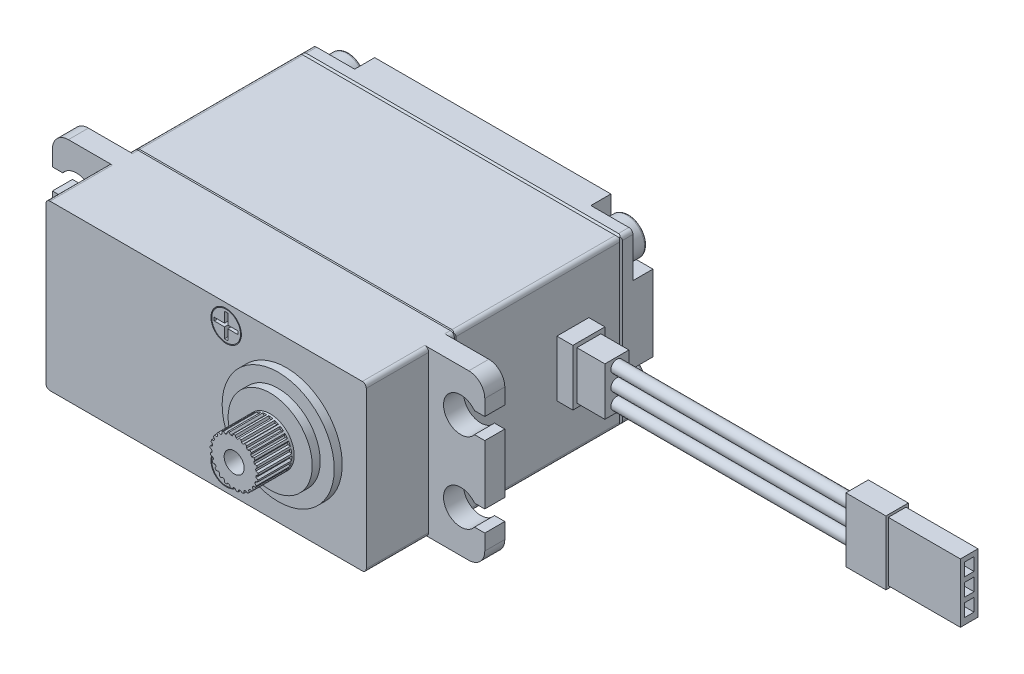
SolidWorks part; units mm, degrees
ref_plane "前视基准面" through (0, 0, 0) normal (0, 0, 1) x (1, 0, 0)
ref_plane "上视基准面" through (0, 0, 0) normal (0, 1, 0) x (1, 0, 0)
ref_plane "右视基准面" through (0, 0, 0) normal (1, 0, 0) x (0, 0, -1)
sketch "草图1" plane through (0, 0, 0) normal (0, 0, 1) x (1, 0, 0)
  line L1 (-20, 10.25) -> (20, 10.25)
  line L2 (-20, 10.25) -> (-20, -10.25)
  line L3 (-20, -10.25) -> (20, -10.25)
  line L4 (20, 10.25) -> (20, -10.25)
  dimension "D1" = 10.25
  dimension "D2" = 20.5
  dimension "D3" = 20
  dimension "D4" = 40
extrude "凸台-拉伸1" add sketch "草图1" along normal blind 4
chamfer "倒角1" distance 0.2 angle 45 4 edges at (0, 10.25, 4) (20, 0, 4) (0, -10.25, 4) (-20, 0, 4)
sketch "草图2" plane through (0, 0, 4) normal (0, 0, 1) x (1, 0, 0)
  line L0 (20, 10.25) -> (20, -10.25) construction
  line L1 (20, -10.25) -> (-20, -10.25) construction
  line L2 (-20, -10.25) -> (-20, 10.25) construction
  line L3 (-20, 10.25) -> (20, 10.25) construction
  line L4 (20, 10.25) -> (20, -10.25)
  line L5 (20, -10.25) -> (-20, -10.25)
  line L6 (-20, -10.25) -> (-20, 10.25)
  line L7 (-20, 10.25) -> (20, 10.25)
extrude "凸台-拉伸2" add sketch "草图2" along normal blind 20.8
chamfer "倒角4" distance 0.2 angle 45 4 edges at (-20, 0, 4) (0, 10.25, 4) (20, 0, 4) (0, -10.25, 4)
chamfer "倒角5" distance 0.2 angle 45 4 edges at (20, 0, 24.8) (0, -10.25, 24.8) (-20, 0, 24.8) (0, 10.25, 24.8)
sketch "草图3" plane through (0, 0, 24.8) normal (0, 0, 1) x (1, 0, 0)
  line L0 (20, 10.25) -> (20, -10.25) construction
  line L1 (20, -10.25) -> (-20, -10.25) construction
  line L2 (-20, -10.25) -> (-20, 10.25) construction
  line L3 (-20, 10.25) -> (20, 10.25) construction
  line L4 (20, 10.25) -> (20, -10.25)
  line L5 (20, -10.25) -> (-20, -10.25)
  line L6 (-20, -10.25) -> (-20, 10.25)
  line L7 (-20, 10.25) -> (20, 10.25)
extrude "凸台-拉伸3" add sketch "草图3" along normal blind 11
sketch "草图4" plane through (0, 0, 35.8) normal (0, 0, 1) x (1, 0, 0)
  line L0 (20, -10.25) -> (20, 10.25) construction
  circle A0 centre (10, 0) radius 7
  dimension "D1" = 10
  dimension "D2" = 14
extrude "凸台-拉伸4" add sketch "草图4" along normal blind 2
sketch "草图5" plane through (0, 0, 37.8) normal (0, 0, 1) x (1, 0, 0)
  circle A0 centre (10, 0) radius 3
  dimension "D1" = 6
extrude "凸台-拉伸5" add sketch "草图5" along normal blind 4.5
ref_plane "基准面1" through (0, 0, 23) normal (0, 0, 1) x (1, 0, 0)
sketch "草图11" plane through (0, 0, 42.3) normal (0, 0, 1) x (1, 0, 0)
  circle A0 centre (10, 0) radius 1.25
  dimension "D1" = 2.5
extrude "切除-拉伸7" cut sketch "草图11" against normal blind 6
sketch "草图12" plane through (0, 0, 42.3) normal (0, 0, 1) x (1, 0, 0)
  line L1 (9.76, 2.7395) -> (9.88, 2.9976)
  line L2 (10.24, 2.7395) -> (10.12, 2.9976)
  line L3 (10.9137, 2.5938) -> (10.8617, 2.8736)
  line L4 (10.4488, 2.7131) -> (10.6292, 2.9333)
  line L5 (11.5301, 2.285) -> (11.5493, 2.569)
  line L6 (11.1095, 2.5163) -> (11.3389, 2.6846)
  line L7 (12.0503, 1.8327) -> (12.1395, 2.103)
  line L8 (11.7004, 2.1613) -> (11.9645, 2.2673)
  line L9 (12.4416, 1.2653) -> (12.5953, 1.5049)
  line L10 (12.1844, 1.6705) -> (12.4667, 1.7075)
  line L11 (12.6796, 0.6183) -> (12.888, 0.8122)
  line L12 (12.5313, 1.0748) -> (12.8138, 1.0404)
  line L13 (12.7492, -0.0675) -> (12.9992, 0.0685)
  line L14 (12.719, 0.4115) -> (12.9841, 0.308)
  line L15 (12.646, -0.7491) -> (12.922, -0.6796)
  line L16 (12.736, -0.2776) -> (12.967, -0.4438)
  line L17 (12.3766, -1.3836) -> (12.6612, -1.3849)
  line L18 (12.581, -0.9493) -> (12.7634, -1.1677)
  line L19 (11.9578, -1.9312) -> (12.2332, -2.0032)
  line L20 (12.2638, -1.5613) -> (12.3862, -1.8183)
  line L21 (11.4161, -2.3574) -> (11.6649, -2.4956)
  line L22 (11.8044, -2.0752) -> (11.859, -2.3546)
  line L23 (10.7853, -2.6355) -> (10.9919, -2.8313)
  line L24 (11.2316, -2.4588) -> (11.2151, -2.7429)
  line L25 (10.1052, -2.748) -> (10.2566, -2.989)
  line L26 (10.5815, -2.6878) -> (10.4948, -2.9589)
  line L27 (9.4185, -2.6878) -> (9.5052, -2.9589)
  line L28 (9.8948, -2.748) -> (9.7434, -2.989)
  line L29 (8.7684, -2.4588) -> (8.7849, -2.7429)
  line L30 (9.2147, -2.6355) -> (9.0081, -2.8313)
  line L31 (8.1956, -2.0752) -> (8.141, -2.3546)
  line L32 (8.5839, -2.3574) -> (8.3351, -2.4956)
  line L33 (7.7362, -1.5613) -> (7.6138, -1.8183)
  line L34 (8.0422, -1.9312) -> (7.7668, -2.0032)
  line L35 (7.419, -0.9493) -> (7.2366, -1.1677)
  line L36 (7.6234, -1.3836) -> (7.3388, -1.3849)
  line L37 (7.264, -0.2776) -> (7.033, -0.4438)
  line L38 (7.354, -0.7491) -> (7.078, -0.6796)
  line L39 (7.281, 0.4115) -> (7.0159, 0.308)
  line L40 (7.2508, -0.0675) -> (7.0008, 0.0685)
  line L41 (7.4687, 1.0748) -> (7.1862, 1.0404)
  line L42 (7.3204, 0.6183) -> (7.112, 0.8122)
  line L43 (7.8156, 1.6705) -> (7.5333, 1.7075)
  line L44 (7.5584, 1.2653) -> (7.4047, 1.5049)
  line L45 (8.2996, 2.1613) -> (8.0355, 2.2673)
  line L46 (7.9497, 1.8327) -> (7.8605, 2.103)
  line L47 (8.8905, 2.5163) -> (8.6611, 2.6846)
  line L48 (8.4699, 2.285) -> (8.4507, 2.569)
  line L49 (9.5512, 2.7131) -> (9.3708, 2.9333)
  line L50 (9.0863, 2.5938) -> (9.1383, 2.8736)
  arc A0 (9.76, 2.7395) -> (9.5512, 2.7131) centre (10, 0) ccw
  arc A1 (9.0863, 2.5938) -> (8.8905, 2.5163) centre (10, 0) ccw
  circle A2 centre (10, 0) radius 3 construction
  arc A3 (9.88, 2.9976) -> (9.3708, 2.9333) centre (10, 0) ccw
  arc A4 (9.1383, 2.8736) -> (8.6611, 2.6846) centre (10, 0) ccw
  arc A5 (8.4699, 2.285) -> (8.2996, 2.1613) centre (10, 0) ccw
  arc A6 (8.4507, 2.569) -> (8.0355, 2.2673) centre (10, 0) ccw
  arc A7 (7.9497, 1.8327) -> (7.8156, 1.6705) centre (10, 0) ccw
  arc A8 (7.8605, 2.103) -> (7.5333, 1.7075) centre (10, 0) ccw
  arc A9 (7.5584, 1.2653) -> (7.4687, 1.0748) centre (10, 0) ccw
  arc A10 (7.4047, 1.5049) -> (7.1862, 1.0404) centre (10, 0) ccw
  arc A11 (7.3204, 0.6183) -> (7.281, 0.4115) centre (10, 0) ccw
  arc A12 (7.112, 0.8122) -> (7.0159, 0.308) centre (10, 0) ccw
  arc A13 (7.2508, -0.0675) -> (7.264, -0.2776) centre (10, 0) ccw
  arc A14 (7.0008, 0.0685) -> (7.033, -0.4438) centre (10, 0) ccw
  arc A15 (7.354, -0.7491) -> (7.419, -0.9493) centre (10, 0) ccw
  arc A16 (7.078, -0.6796) -> (7.2366, -1.1677) centre (10, 0) ccw
  arc A17 (7.3388, -1.3849) -> (7.6138, -1.8183) centre (10, 0) ccw
  arc A18 (7.6234, -1.3836) -> (7.7362, -1.5613) centre (10, 0) ccw
  arc A19 (8.0422, -1.9312) -> (8.1956, -2.0752) centre (10, 0) ccw
  arc A20 (7.7668, -2.0032) -> (8.141, -2.3546) centre (10, 0) ccw
  arc A21 (8.5839, -2.3574) -> (8.7684, -2.4588) centre (10, 0) ccw
  arc A22 (8.3351, -2.4956) -> (8.7849, -2.7429) centre (10, 0) ccw
  arc A23 (9.2147, -2.6355) -> (9.4185, -2.6878) centre (10, 0) ccw
  arc A24 (9.0081, -2.8313) -> (9.5052, -2.9589) centre (10, 0) ccw
  arc A25 (9.8948, -2.748) -> (10.1052, -2.748) centre (10, 0) ccw
  arc A26 (9.7434, -2.989) -> (10.2566, -2.989) centre (10, 0) ccw
  arc A27 (10.5815, -2.6878) -> (10.7853, -2.6355) centre (10, 0) ccw
  arc A28 (10.4948, -2.9589) -> (10.9919, -2.8313) centre (10, 0) ccw
  arc A29 (11.2316, -2.4588) -> (11.4161, -2.3574) centre (10, 0) ccw
  arc A30 (11.2151, -2.7429) -> (11.6649, -2.4956) centre (10, 0) ccw
  arc A31 (11.8044, -2.0752) -> (11.9578, -1.9312) centre (10, 0) ccw
  arc A32 (11.859, -2.3546) -> (12.2332, -2.0032) centre (10, 0) ccw
  arc A33 (12.3862, -1.8183) -> (12.6612, -1.3849) centre (10, 0) ccw
  arc A34 (12.2638, -1.5613) -> (12.3766, -1.3836) centre (10, 0) ccw
  arc A35 (12.7634, -1.1677) -> (12.922, -0.6796) centre (10, 0) ccw
  arc A36 (12.581, -0.9493) -> (12.646, -0.7491) centre (10, 0) ccw
  arc A37 (12.967, -0.4438) -> (12.9992, 0.0685) centre (10, 0) ccw
  arc A38 (12.736, -0.2776) -> (12.7492, -0.0675) centre (10, 0) ccw
  arc A39 (12.9841, 0.308) -> (12.888, 0.8122) centre (10, 0) ccw
  arc A40 (12.719, 0.4115) -> (12.6796, 0.6183) centre (10, 0) ccw
  arc A41 (12.5313, 1.0748) -> (12.4416, 1.2653) centre (10, 0) ccw
  arc A42 (12.8138, 1.0404) -> (12.5953, 1.5049) centre (10, 0) ccw
  arc A43 (12.1844, 1.6705) -> (12.0503, 1.8327) centre (10, 0) ccw
  arc A44 (12.4667, 1.7075) -> (12.1395, 2.103) centre (10, 0) ccw
  arc A45 (11.7004, 2.1613) -> (11.5301, 2.285) centre (10, 0) ccw
  arc A46 (11.9645, 2.2673) -> (11.5493, 2.569) centre (10, 0) ccw
  arc A47 (11.1095, 2.5163) -> (10.9137, 2.5938) centre (10, 0) ccw
  arc A48 (11.3389, 2.6846) -> (10.8617, 2.8736) centre (10, 0) ccw
  arc A49 (10.4488, 2.7131) -> (10.24, 2.7395) centre (10, 0) ccw
  arc A50 (10.6292, 2.9333) -> (10.12, 2.9976) centre (10, 0) ccw
  point P111 (10, 0)
  dimension "D1" = 5.5
  dimension "D4" = 25
extrude "切除-拉伸8" cut sketch "草图12" against normal blind 4.2
sketch "草图17" plane through (20, 0, 0) normal (1, 0, 0) x (0, 0, -1)
  line L2 (-12, 3.5) -> (-8, 3.5)
  line L3 (-12, 3.5) -> (-12, -3.5)
  line L4 (-12, -3.5) -> (-8, -3.5)
  line L5 (-8, 3.5) -> (-8, -3.5)
  dimension "D2" = 7
  dimension "D3" = 3.5
  dimension "D4" = 4
extrude "凸台-拉伸8" add sketch "草图17" along normal blind 2
sketch "草图18" plane through (22, 0, 0) normal (1, 0, 0) x (0, 0, -1)
  line L8 (-11.5, 3) -> (-11.5, -3)
  line L9 (-11.5, -3) -> (-8.5, -3)
  line L10 (-8.5, -3) -> (-8.5, 3)
  line L11 (-8.5, 3) -> (-11.5, 3)
  line L12 (-11.5, 3) -> (-11.5, -3)
  line L13 (-11.5, -3) -> (-8.5, -3)
  line L14 (-8.5, -3) -> (-8.5, 3)
  line L15 (-8.5, 3) -> (-11.5, 3)
  dimension "D1" = 0.5
extrude "凸台-拉伸9" add sketch "草图18" along normal blind 3.5
sketch "草图19" plane through (25.5, 0, 0) normal (1, 0, 0) x (0, 0, -1)
  line L0 (-8.5, -3) -> (-8.5, 3) construction
  line L1 (-8.5, -3) -> (-8.5, 3) construction
  line L2 (-8.5, 3) -> (-11.5, 3) construction
  circle A0 centre (-10, 0) radius 0.75
  circle A1 centre (-10, 2) radius 0.75
  circle A2 centre (-10, -2) radius 0.75
  dimension "D1" = 1.5
  dimension "D2" = 1.5
  dimension "D3" = 1.5
  dimension "D4" = 1.5
  dimension "D5" = 1.5
  dimension "D6" = 1.5
  dimension "D7" = 1
  dimension "D8" = 2
  dimension "D9" = 2
extrude "凸台-拉伸10" add sketch "草图19" along normal blind 30
sketch "草图20" plane through (55.5, 0, 0) normal (1, 0, 0) x (0, 0, -1)
  line L1 (-11.4, 4) -> (-8.6, 4)
  line L2 (-11.4, 4) -> (-11.4, -4)
  line L3 (-11.4, -4) -> (-8.6, -4)
  line L4 (-8.6, 4) -> (-8.6, -4)
  circle A0 centre (-10, 2) radius 0.75 construction
  dimension "D1" = 8
  dimension "D2" = 2.8
  dimension "D3" = 1.4
  dimension "D4" = 4
extrude "凸台-拉伸11" add sketch "草图20" along normal blind 5
sketch "草图21" plane through (60.5, 0, 0) normal (1, 0, 0) x (0, 0, -1)
  line L5 (-10.59, 3.1) -> (-9.4, 3.1)
  line L6 (-10.59, 3.1) -> (-10.59, 1.5)
  line L7 (-10.59, 1.5) -> (-9.4, 1.5)
  line L8 (-11.1, 3.7) -> (-11.1, -3.7)
  line L9 (-11.1, -3.7) -> (-8.9, -3.7)
  line L10 (-8.9, -3.7) -> (-8.9, 3.7)
  line L11 (-8.9, 3.7) -> (-11.1, 3.7)
  line L12 (-11.1, 3.7) -> (-11.1, -3.7)
  line L13 (-11.1, -3.7) -> (-8.9, -3.7)
  line L14 (-8.9, -3.7) -> (-8.9, 3.7)
  line L15 (-8.9, 3.7) -> (-11.1, 3.7)
  line L16 (-9.4, 3.1) -> (-9.4, 1.5)
  line L17 (-10.59, 0.9) -> (-9.4, 0.9)
  line L18 (-10.59, 0.9) -> (-10.59, -0.7)
  line L19 (-10.59, -0.7) -> (-9.4, -0.7)
  line L20 (-9.4, 0.9) -> (-9.4, -0.7)
  line L21 (-10.59, -1.3) -> (-9.4, -1.3)
  line L22 (-10.59, -1.3) -> (-10.59, -2.9)
  line L23 (-10.59, -2.9) -> (-9.4, -2.9)
  line L24 (-9.4, -1.3) -> (-9.4, -2.9)
  dimension "D2" = 1.6
  dimension "D3" = 1.6
  dimension "D4" = 1.6
  dimension "D5" = 0.5
  dimension "D6" = 0.5
  dimension "D7" = 0.5
  dimension "D8" = 0.6
  dimension "D9" = 0.6
  dimension "D10" = 0.6
  dimension "D1" = 0.3
extrude "凸台-拉伸12" add sketch "草图21" along normal blind 9
sketch "草图22" plane through (0, 0, 0) normal (0, 0, -1) x (-1, 0, 0)
  line L5 (-20, 4.75) -> (-20, 10.25)
  line L6 (-20, 10.25) -> (-14.75, 10.25)
  line L7 (-17.5, -4.75) -> (-20, -4.75)
  line L8 (-14.75, -7.5) -> (-14.75, -10.25)
  line L9 (-20, -4.75) -> (-20, -10.25)
  line L11 (-20, -10.25) -> (-14.75, -10.25)
  line L12 (-14.75, 7.5) -> (-14.75, 10.25)
  line L13 (-17.5, 4.75) -> (-20, 4.75)
  line L14 (14.75, -7.5) -> (14.75, -10.25)
  line L15 (20, -10.25) -> (14.75, -10.25)
  line L16 (20, -4.75) -> (20, -10.25)
  line L17 (17.5, -4.75) -> (20, -4.75)
  line L18 (20, 4.75) -> (20, 10.25)
  line L19 (17.5, 4.75) -> (20, 4.75)
  line L20 (14.75, 7.5) -> (14.75, 10.25)
  line L21 (20, 10.25) -> (14.75, 10.25)
  arc A0 (-14.75, -7.5) -> (-17.5, -4.75) centre (-17.5, -7.5) ccw
  arc A1 (-14.75, 7.5) -> (-17.5, 4.75) centre (-17.5, 7.5) cw
  arc A2 (14.75, -7.5) -> (17.5, -4.75) centre (17.5, -7.5) cw
  arc A3 (14.75, 7.5) -> (17.5, 4.75) centre (17.5, 7.5) ccw
  dimension "D3" = 5.5
extrude "切除-拉伸13" cut sketch "草图22" against normal blind 2.5
sketch "草图23" plane through (0, 0, 2.5) normal (0, 0, -1) x (-1, 0, 0)
  line L4 (-17.25, -7.75) -> (-15.6165, -7.75)
  line L5 (-17.25, -7.25) -> (-15.6165, -7.25)
  line L6 (-17.25, 7.25) -> (-17.25, 5.6165)
  line L7 (-17.25, 7.75) -> (-15.6165, 7.75)
  line L8 (-17.25, -7.25) -> (-17.25, -5.6165)
  line L9 (-17.75, 7.25) -> (-17.75, 5.6165)
  line L10 (-17.75, -7.25) -> (-17.75, -5.6165)
  line L11 (-17.25, 7.25) -> (-15.6165, 7.25)
  line L12 (-19.3835, -7.25) -> (-17.75, -7.25)
  line L13 (-19.3835, -7.75) -> (-17.75, -7.75)
  line L14 (-17.75, -9.3835) -> (-17.75, -7.75)
  line L15 (-17.25, -9.3835) -> (-17.25, -7.75)
  line L16 (-19.3835, 7.25) -> (-17.75, 7.25)
  line L17 (-19.3835, 7.75) -> (-17.75, 7.75)
  line L18 (-17.25, 9.3835) -> (-17.25, 7.75)
  line L19 (-17.75, 9.3835) -> (-17.75, 7.75)
  line L20 (17.25, -7.25) -> (15.6165, -7.25)
  line L21 (17.25, -7.75) -> (15.6165, -7.75)
  line L22 (17.25, -9.3835) -> (17.25, -7.75)
  line L23 (17.75, -9.3835) -> (17.75, -7.75)
  line L24 (19.3835, -7.75) -> (17.75, -7.75)
  line L25 (19.3835, -7.25) -> (17.75, -7.25)
  line L26 (17.75, -7.25) -> (17.75, -5.6165)
  line L27 (17.25, -7.25) -> (17.25, -5.6165)
  line L28 (19.3835, 7.25) -> (17.75, 7.25)
  line L29 (17.75, 7.25) -> (17.75, 5.6165)
  line L30 (17.25, 7.25) -> (17.25, 5.6165)
  line L31 (17.25, 7.25) -> (15.6165, 7.25)
  line L32 (17.25, 7.75) -> (15.6165, 7.75)
  line L33 (17.25, 9.3835) -> (17.25, 7.75)
  line L34 (17.75, 9.3835) -> (17.75, 7.75)
  line L35 (19.3835, 7.75) -> (17.75, 7.75)
  circle A0 centre (-17.5, 7.5) radius 2.25
  arc A1 (-15.6165, 7.25) -> (-15.6165, 7.75) centre (-17.5, 7.5) ccw
  arc A2 (-17.75, 5.6165) -> (-17.25, 5.6165) centre (-17.5, 7.5) ccw
  arc A3 (-19.3835, 7.75) -> (-19.3835, 7.25) centre (-17.5, 7.5) ccw
  arc A4 (-17.25, 9.3835) -> (-17.75, 9.3835) centre (-17.5, 7.5) ccw
  arc A5 (-17.75, -5.6165) -> (-17.25, -5.6165) centre (-17.5, -7.5) cw
  arc A6 (-15.6165, -7.25) -> (-15.6165, -7.75) centre (-17.5, -7.5) cw
  arc A7 (-19.3835, -7.75) -> (-19.3835, -7.25) centre (-17.5, -7.5) cw
  arc A8 (-17.25, -9.3835) -> (-17.75, -9.3835) centre (-17.5, -7.5) cw
  circle A9 centre (-17.5, -7.5) radius 2.25
  arc A10 (15.6165, -7.25) -> (15.6165, -7.75) centre (17.5, -7.5) ccw
  arc A11 (17.25, -9.3835) -> (17.75, -9.3835) centre (17.5, -7.5) ccw
  arc A12 (19.3835, -7.75) -> (19.3835, -7.25) centre (17.5, -7.5) ccw
  arc A13 (17.75, -5.6165) -> (17.25, -5.6165) centre (17.5, -7.5) ccw
  circle A14 centre (17.5, -7.5) radius 2.25
  arc A15 (17.75, 5.6165) -> (17.25, 5.6165) centre (17.5, 7.5) cw
  arc A16 (19.3835, 7.75) -> (19.3835, 7.25) centre (17.5, 7.5) cw
  arc A17 (15.6165, 7.25) -> (15.6165, 7.75) centre (17.5, 7.5) cw
  arc A18 (17.25, 9.3835) -> (17.75, 9.3835) centre (17.5, 7.5) cw
  circle A19 centre (17.5, 7.5) radius 2.25
  point P8 (-19.75, 7.25)
  point P9 (-13.9428, 7.25)
  point P10 (-17.75, 9.75)
  point P11 (-17.75, 5.25)
  point P12 (-19.75, 7.75)
  point P13 (-13.9428, 7.75)
  point P14 (-17.25, 9.75)
  point P15 (-17.25, 5.25)
  dimension "D1" = 4.5
  dimension "D2" = 3.8
extrude "凸台-拉伸13" add sketch "草图23" along normal blind 2
fillet "圆角2" radius 0.3 4 edges at (-19.75, -7.5, 0.5) (19.75, -7.5, 0.5) (15.25, 7.5, 0.5) (-15.25, 7.5, 0.5)
chamfer "倒角6" distance 0.5 angle 45 1 edges at (17, 0, 37.8)
fillet "圆角6" radius 0.5 4 edges at (20, 10.25, 30.3) (20, -10.25, 30.3) (-20, 10.25, 30.3) (-20, -10.25, 30.3)
fillet "圆角7" radius 0.5 4 edges at (20, -10.25, 14.4) (20, 10.25, 14.4) (-20, 10.25, 14.4) (-20, -10.25, 14.4)
fillet "圆角8" radius 0.5 4 edges at (20, 10.25, 3.15) (-20, 10.25, 3.15) (-20, -10.25, 3.15) (20, -10.25, 3.15)
sketch "草图24" plane through (0, 0, 37.8) normal (0, 0, 1) x (1, 0, 0)
  circle A0 centre (10, 0) radius 5.25
  circle A3 centre (10, 0) radius 7 construction
  circle A4 centre (10, 0) radius 7
  dimension "D1" = 10.5
extrude "切除-拉伸14" cut sketch "草图24" against normal blind 1
ref_plane "基准面2" through (0, 0, 25.5) normal (0, 0, -1) x (-1, 0, 0)
sketch "草图25" plane through (0, 0, 25.5) normal (0, 0, -1) x (-1, 0, 0)
  line L5 (27, 10.25) -> (27, 6.3)
  line L6 (19.5, 10.25) -> (27, 10.25)
  line L8 (19.5, -10.25) -> (27, -10.25)
  line L10 (20, 4.75) -> (20, 9.75) construction
  line L11 (20, 4.75) -> (20, 9.75)
  line L12 (20, 9.75) -> (20, -9.75)
  line L13 (25.7125, -3.7) -> (27, -3.7)
  line L15 (25.7125, 3.7) -> (27, 3.7)
  line L16 (25.7125, 6.3) -> (27, 6.3)
  line L17 (27, 3.7) -> (27, -3.7)
  line L18 (25.7125, -6.3) -> (27, -6.3)
  line L19 (27, -6.3) -> (27, -10.25)
  line L20 (-27, -6.3) -> (-27, -10.25)
  line L21 (-25.7125, -6.3) -> (-27, -6.3)
  line L22 (-27, 3.7) -> (-27, -3.7)
  line L23 (-25.7125, 6.3) -> (-27, 6.3)
  line L24 (-25.7125, 3.7) -> (-27, 3.7)
  line L25 (-25.7125, -3.7) -> (-27, -3.7)
  line L26 (-20, 9.75) -> (-20, -9.75)
  line L27 (-20, 4.75) -> (-20, 9.75)
  line L28 (-19.5, -10.25) -> (-27, -10.25)
  line L29 (-19.5, 10.25) -> (-27, 10.25)
  line L30 (-27, 10.25) -> (-27, 6.3)
  arc A0 (20, 9.75) -> (19.5, 10.25) centre (19.5, 9.75) ccw construction
  arc A1 (20, 9.75) -> (19.5, 10.25) centre (19.5, 9.75) ccw
  arc A2 (19.5, -10.25) -> (20, -9.75) centre (19.5, -9.75) ccw construction
  arc A3 (19.5, -10.25) -> (20, -9.75) centre (19.5, -9.75) ccw
  arc A4 (25.7125, 6.3) -> (25.7125, 3.7) centre (24, 5) ccw
  arc A5 (25.7125, -6.3) -> (25.7125, -3.7) centre (24, -5) cw
  arc A6 (-25.7125, -6.3) -> (-25.7125, -3.7) centre (-24, -5) ccw
  arc A7 (-25.7125, 6.3) -> (-25.7125, 3.7) centre (-24, 5) cw
  arc A8 (-19.5, -10.25) -> (-20, -9.75) centre (-19.5, -9.75) cw
  arc A9 (-20, 9.75) -> (-19.5, 10.25) centre (-19.5, 9.75) cw
  point P12 (27, -12.95)
  point P18 (24, 3.7)
  point P20 (29.0926, 3.7)
  point P28 (24, 6.3)
  point P29 (29.0926, 6.3)
extrude "凸台-拉伸14" add sketch "草图25" against normal blind 2.5 contours L18 A5 L13 L17 L15 A4 L16 L5 L6 A1 L11 L12 A3 L8 L19 | L26 A9 L29 L30 L23 A7 L24 L22 L25 A6 L21 L20 L28 A8 region at (-23.2228, 0, 25.5) region at (23.2228, 0, 25.5)
fillet "圆角9" radius 2 4 edges at (-27, 10.25, 26.75) (27, 10.25, 26.75) (27, -10.25, 26.75) (-27, -10.25, 26.75)
sketch "草图26" plane through (0, 0, 35.8) normal (0, 0, 1) x (1, 0, 0)
  line L0 (19.5, 10.25) -> (-19.5, 10.25) construction
  circle A3 centre (2.5, 7.75) radius 1.9
  circle A4 centre (2.5, -7.75) radius 1.9
  dimension "D1" = 3.8
  dimension "D2" = 2.5
extrude "切除-拉伸15" cut sketch "草图26" against normal blind 1.3
sketch "草图27" plane through (0, 0, 34.5) normal (0, 0, 1) x (1, 0, 0)
  line L10 (2.7, 7.95) -> (3.9866, 7.95)
  line L12 (2.3, 7.95) -> (2.3, 9.2366)
  line L14 (2.7, 7.55) -> (3.9866, 7.55)
  line L16 (2.7, 7.95) -> (2.7, 9.2366)
  line L17 (2.7, 6.2634) -> (2.7, 7.55)
  line L18 (1.0134, 7.55) -> (2.3, 7.55)
  line L19 (2.3, 6.2634) -> (2.3, 7.55)
  line L20 (1.0134, 7.95) -> (2.3, 7.95)
  arc A8 (1.0134, 7.55) -> (1.0134, 7.95) centre (2.5, 7.75) cw
  arc A9 (2.3, 9.2366) -> (2.7, 9.2366) centre (2.5, 7.75) cw
  arc A10 (3.9866, 7.95) -> (3.9866, 7.55) centre (2.5, 7.75) cw
  arc A11 (2.7, 6.2634) -> (2.3, 6.2634) centre (2.5, 7.75) cw
  circle A13 centre (2.5, 7.75) radius 1.8
  point P12 (1, -7.95)
  point P13 (4.4, -7.95)
  point P14 (2.3, -6.25)
  point P15 (2.3, -9.3797)
  point P16 (1, -7.55)
  point P17 (4.4, -7.55)
  point P18 (2.7, -6.25)
  point P19 (2.7, -9.3797)
extrude "凸台-拉伸16" add sketch "草图27" along normal blind 1.3 contours A13 L17 A11 L19 L18 A8 L20 L12 A9 L16 L10 A10 L14
mirror "镜向1" about plane through (0, 0, 0) normal (0, 1, 0) of "凸台-拉伸16"
